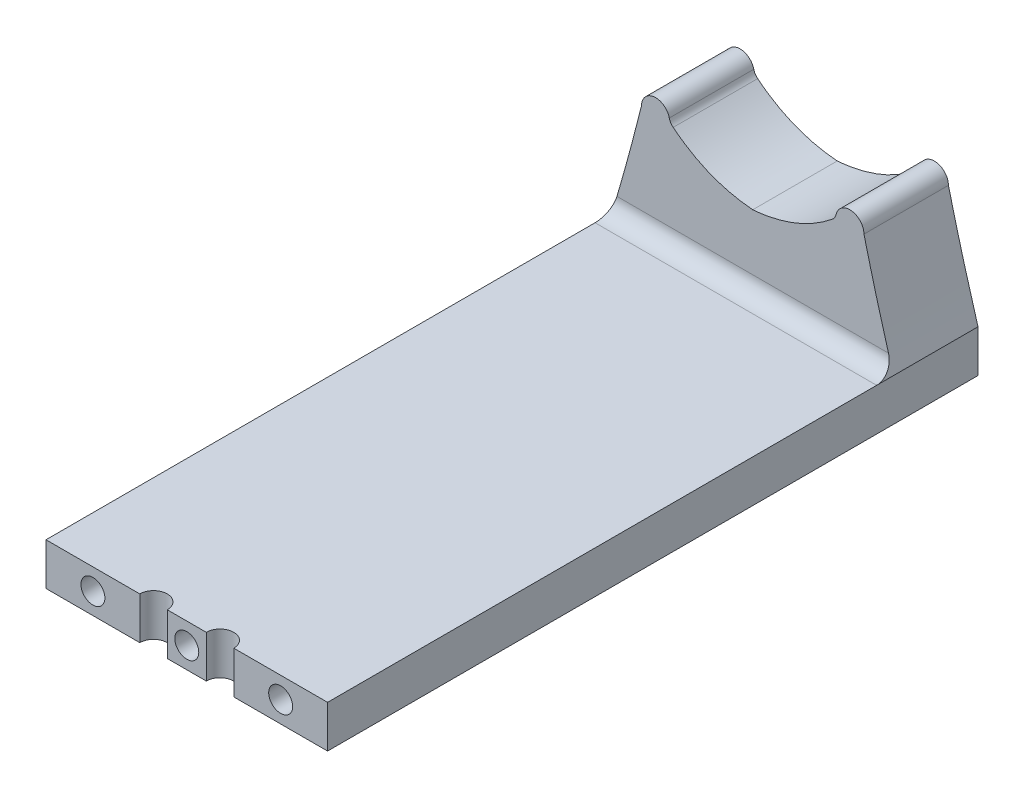
SolidWorks part; units mm, degrees
ref_plane "Front Plane" through (0, 0, 0) normal (0, 0, 1) x (1, 0, 0)
ref_plane "Top Plane" through (0, 0, 0) normal (0, 1, 0) x (1, 0, 0)
ref_plane "Right Plane" through (0, 0, 0) normal (1, 0, 0) x (0, 0, -1)
sketch "Sketch1" plane through (0, 0, 0) normal (0, 0, 1) x (1, 0, 0)
  line L0 (-996.8903, -40.64) -> (49003.1097, -40.64) construction
  line L1 (0, -1000) -> (0, 49000) construction
  line L2 (0, 0) -> (-23.4635, -40.64) construction
  line L3 (0, 0) -> (-40.64, -40.64) construction
  line L4 (-31.75, -62.23) -> (-31.75, -71.755)
  line L5 (-31.75, -71.755) -> (31.75, -71.755)
  line L6 (31.75, -62.23) -> (31.75, -71.755)
  line L7 (-957.5735, -46.99) -> (49042.4265, -46.99) construction
  circle A0 centre (0, 0) radius 40.64 construction
  arc A1 (-18.7325, -37.9449) -> (-25.0825, -37.9449) centre (-21.9075, -37.9449) ccw
  arc A2 (18.7325, -37.9449) -> (25.0825, -37.9449) centre (21.9075, -37.9449) cw
  spline S0 degree 2 poles (-18.7325, -37.9449) (-10.6333, -44.8669) (0, -45.72) knots 0 0 0 1 1 1
  spline S1 degree 2 poles (-25.0825, -37.9449) (-28.1202, -50.167) (-31.75, -62.23) knots 0 0 0 1 1 1
  spline S2 degree 2 poles (25.0825, -37.9449) (28.1202, -50.167) (31.75, -62.23) knots 0 0 0 1 1 1
  spline S3 degree 2 poles (18.7325, -37.9449) (10.6333, -44.8669) (0, -45.72) knots 0 0 0 1 1 1
  point P13 (0, -71.755)
  dimension "D1" = 81.28
  dimension "D3" = 6.35
  dimension "D5" = 5.08
  dimension "D2" = 30
  dimension "D4" = 45
  dimension "D6" = 31.75
  dimension "D7" = 9.525
  dimension "D8" = 21.59
  dimension "D9" = 6.35
extrude "Boss-Extrude1" add sketch "Sketch1" along normal mid plane 19.05
sketch "Sketch2" plane through (0, 0, 0) normal (0, 0, 1) x (1, 0, 0)
  line L1 (-31.75, -62.23) -> (31.75, -62.23)
  line L2 (-31.75, -62.23) -> (-31.75, -71.755)
  line L3 (-31.75, -71.755) -> (31.75, -71.755)
  line L4 (31.75, -62.23) -> (31.75, -71.755)
extrude "Boss-Extrude2" add sketch "Sketch2" along normal blind 137.16
fillet "Fillet2" radius 2.54 2 edges at (18.7325, -37.9449, 0) (-18.7325, -37.9449, 0)
sketch "Sketch3" plane through (0, -62.23, 0) normal (0, 1, 0) x (1, 0, 0)
  line L0 (31.75, -137.16) -> (-31.75, -137.16) construction
  line L1 (0, -9.525) -> (0, 9.525) construction
  circle A0 centre (7.5, -137.16) radius 3.1
  circle A1 centre (-7.5, -137.16) radius 3.1
  dimension "D1" = 6.2
  dimension "D2" = 7.5
extrude "Cut-Extrude1" cut sketch "Sketch3" against normal through all
ref_plane "wheel_tangent_plane" through (0, -40.64, 0) normal (0, 1, 0) x (1, 0, 0)
ref_plane "offset_0.1in_aka_poly_top" through (0, -43.18, 0) normal (0, 1, 0) x (1, 0, 0)
sketch "Sketch4" plane through (0, 0, 137.16) normal (0, 0, 1) x (1, 0, 0)
  circle A0 centre (-21.175, -66.9925) radius 2.7
  circle A1 centre (0, -66.9925) radius 2.7
  circle A2 centre (21.175, -66.9925) radius 2.7
  dimension "D1" = 5.4
  dimension "D2" = 5.4
  dimension "D3" = 5.4
extrude "Cut-Extrude2" cut sketch "Sketch4" against normal blind 9.525
fillet "Fillet3" radius 3.81 1 edges at (0, -62.23, 9.525) type face fillet first side face at (2.7343, -43.5854, 9.525) second side face at (0, -62.23, 104.4763)
